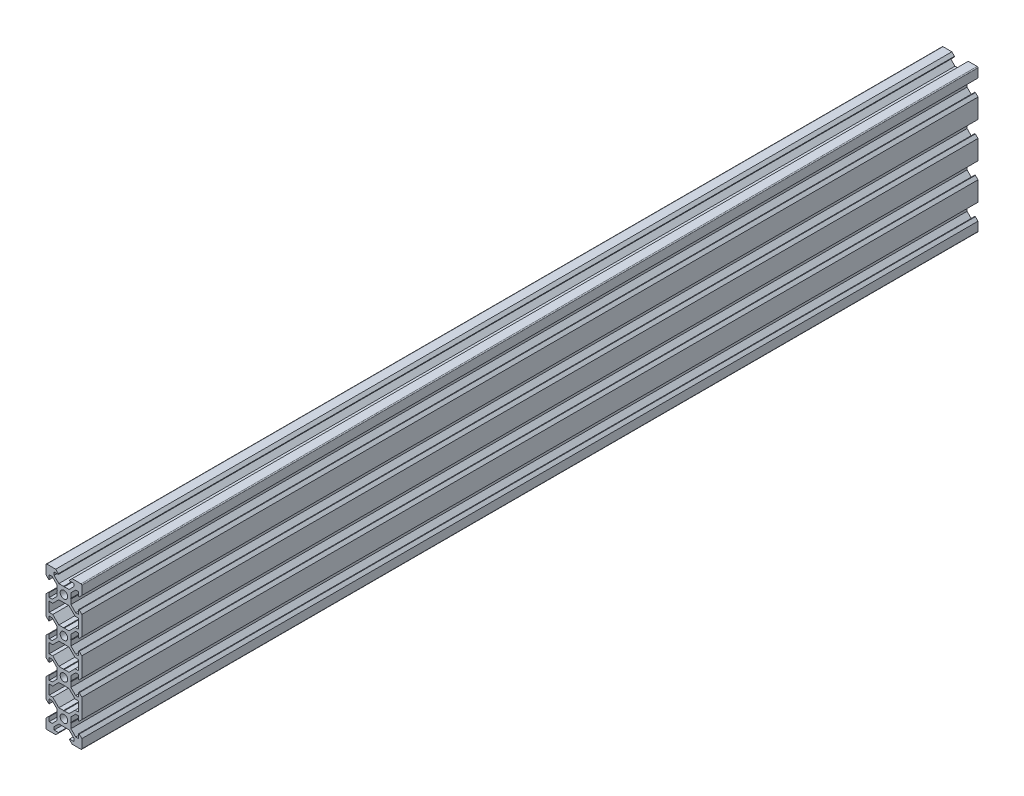
SolidWorks part; units mm, degrees
ref_plane "Plan de face" through (0, 0, 0) normal (0, 0, 1) x (1, 0, 0)
ref_plane "Plan de dessus" through (0, 0, 0) normal (0, 1, 0) x (1, 0, 0)
ref_plane "Plan de droite" through (0, 0, 0) normal (1, 0, 0) x (0, 0, -1)
ref_axis "Axe" through (0, 0, -13.782) along (0, 0, 1)
sketch "Esquisse1" plane through (0, 0, 0) normal (0, 0, 1) x (1, 0, 0)
  line L0 (0, 27.6392) -> (0, -27.6392) construction
  line L1 (-33.6074, 0) -> (33.6074, 0) construction
  line L2 (0, 0) -> (-22.2114, 22.2114) construction
  line L3 (-9.5, 10) -> (-4.58, 10)
  line L4 (-4.58, 10) -> (-3.125, 8.545)
  line L5 (-3.125, 8.545) -> (-3.125, 8.2)
  line L6 (-3.125, 8.2) -> (-5.5, 8.2)
  line L7 (-2.8393, 3.9) -> (-5.5, 6.5607)
  line L8 (-2.8393, 3.9) -> (-0.21, 3.9)
  line L9 (-5.5, 6.5607) -> (-5.5, 8.2)
  line L10 (0, 3.69) -> (0, 2.1)
  line L11 (-3.9, 2.8393) -> (-6.5607, 5.5)
  line L12 (-8.545, 3.125) -> (-8.2, 3.125)
  line L13 (-8.2, 3.125) -> (-8.2, 5.5)
  line L14 (-6.5607, 5.5) -> (-8.2, 5.5)
  line L15 (-10, 4.58) -> (-8.545, 3.125)
  line L16 (-10, 9.5) -> (-10, 4.58)
  line L17 (-0.21, 3.9) -> (0, 3.69)
  line L18 (-3.9, 2.8393) -> (-3.9, 0.21)
  line L19 (-6.2393, -12.7) -> (-8.2, -12.7)
  line L20 (-3.9, 0.21) -> (-3.69, 0)
  line L21 (-0.21, -3.9) -> (0, -3.69)
  line L22 (0, -3.69) -> (0, -2.1)
  line L23 (-6.5607, -5.5) -> (-8.2, -5.5)
  line L24 (-2.8393, -3.9) -> (-0.21, -3.9)
  line L25 (-8.545, -3.125) -> (-8.2, -3.125)
  line L26 (-10, -4.58) -> (-8.545, -3.125)
  line L27 (-8.2, -3.125) -> (-8.2, -5.5)
  line L28 (-2.8393, -3.9) -> (-6.2393, -7.3)
  line L29 (-3.9, -2.8393) -> (-6.5607, -5.5)
  line L30 (-3.9, -2.8393) -> (-3.9, -0.21)
  line L31 (-3.9, -0.21) -> (-3.69, 0)
  line L32 (-6.2393, -7.3) -> (-8.2, -7.3)
  line L33 (-8.2, -7.3) -> (-8.2, -12.7)
  line L34 (-8.2, -10) -> (-10, -10) construction
  line L35 (-10, -15.42) -> (-10, -4.58)
  line L36 (-3.9, -19.79) -> (-3.69, -20)
  line L37 (-3.9, -17.1607) -> (-3.9, -19.79)
  line L38 (-3.9, -17.1607) -> (-6.5607, -14.5)
  line L39 (-2.8393, -16.1) -> (-6.2393, -12.7)
  line L40 (-8.2, -16.875) -> (-8.2, -14.5)
  line L41 (-10, -15.42) -> (-8.545, -16.875)
  line L42 (-8.545, -16.875) -> (-8.2, -16.875)
  line L43 (-2.8393, -16.1) -> (-0.21, -16.1)
  line L44 (-6.5607, -14.5) -> (-8.2, -14.5)
  line L45 (0, -16.31) -> (0, -17.9)
  line L46 (-0.21, -16.1) -> (0, -16.31)
  line L47 (-8.2, -30) -> (-10, -30) construction
  line L48 (-3.69, -20) -> (0, -20) construction
  line L49 (-0.21, -23.9) -> (0, -23.69)
  line L50 (0, -23.69) -> (0, -22.1)
  line L51 (-6.5607, -25.5) -> (-8.2, -25.5)
  line L52 (-2.8393, -23.9) -> (-0.21, -23.9)
  line L53 (-8.545, -23.125) -> (-8.2, -23.125)
  line L54 (-10, -24.58) -> (-8.545, -23.125)
  line L55 (-8.2, -23.125) -> (-8.2, -25.5)
  line L56 (-2.8393, -23.9) -> (-6.2393, -27.3)
  line L57 (-3.9, -22.8393) -> (-6.5607, -25.5)
  line L58 (-3.9, -22.8393) -> (-3.9, -20.21)
  line L59 (-3.9, -20.21) -> (-3.69, -20)
  line L60 (-10, -24.58) -> (-10, -35.42)
  line L61 (-8.2, -32.7) -> (-8.2, -27.3)
  line L62 (-3.69, -40) -> (0, -40) construction
  line L63 (-8.2, -50) -> (-10, -50) construction
  line L64 (0, -60) -> (-22.2114, -82.2114) construction
  line L65 (-33.6074, -60) -> (33.6074, -60) construction
  line L66 (0, -87.6392) -> (0, -32.3608) construction
  line L67 (-6.2393, -32.7) -> (-8.2, -32.7)
  line L68 (-3.9, -39.79) -> (-3.69, -40)
  line L69 (-3.9, -37.1607) -> (-3.9, -39.79)
  line L70 (-3.9, -37.1607) -> (-6.5607, -34.5)
  line L71 (-2.8393, -36.1) -> (-6.2393, -32.7)
  line L72 (-8.2, -36.875) -> (-8.2, -34.5)
  line L73 (-10, -35.42) -> (-8.545, -36.875)
  line L74 (-8.545, -36.875) -> (-8.2, -36.875)
  line L75 (-6.2393, -27.3) -> (-8.2, -27.3)
  line L76 (-2.8393, -36.1) -> (-0.21, -36.1)
  line L77 (-6.5607, -34.5) -> (-8.2, -34.5)
  line L78 (0, -36.31) -> (0, -37.9)
  line L79 (-0.21, -36.1) -> (0, -36.31)
  line L80 (-0.21, -43.9) -> (0, -43.69)
  line L81 (0, -43.69) -> (0, -42.1)
  line L82 (-6.5607, -45.5) -> (-8.2, -45.5)
  line L83 (-2.8393, -43.9) -> (-0.21, -43.9)
  line L84 (-8.545, -43.125) -> (-8.2, -43.125)
  line L85 (-10, -44.58) -> (-8.545, -43.125)
  line L86 (-8.2, -43.125) -> (-8.2, -45.5)
  line L87 (-2.8393, -43.9) -> (-6.2393, -47.3)
  line L88 (-3.9, -42.8393) -> (-6.5607, -45.5)
  line L89 (-3.9, -42.8393) -> (-3.9, -40.21)
  line L90 (-3.9, -40.21) -> (-3.69, -40)
  line L91 (-10, -44.58) -> (-10, -55.42)
  line L92 (-8.2, -52.7) -> (-8.2, -47.3)
  line L93 (-6.2393, -52.7) -> (-8.2, -52.7)
  line L94 (-3.9, -59.79) -> (-3.69, -60)
  line L95 (-3.9, -57.1607) -> (-3.9, -59.79)
  line L96 (-3.9, -57.1607) -> (-6.5607, -54.5)
  line L97 (-2.8393, -56.1) -> (-6.2393, -52.7)
  line L98 (-8.2, -56.875) -> (-8.2, -54.5)
  line L99 (-10, -55.42) -> (-8.545, -56.875)
  line L100 (-8.545, -56.875) -> (-8.2, -56.875)
  line L101 (-2.8393, -56.1) -> (-0.21, -56.1)
  line L102 (-6.5607, -54.5) -> (-8.2, -54.5)
  line L103 (0, -56.31) -> (0, -57.9)
  line L104 (-0.21, -56.1) -> (0, -56.31)
  line L105 (-3.9, -60.21) -> (-3.69, -60)
  line L106 (-6.2393, -47.3) -> (-8.2, -47.3)
  line L107 (-3.9, -62.8393) -> (-3.9, -60.21)
  line L108 (-0.21, -63.9) -> (0, -63.69)
  line L109 (-10, -69.5) -> (-10, -64.58)
  line L110 (-10, -64.58) -> (-8.545, -63.125)
  line L111 (-6.5607, -65.5) -> (-8.2, -65.5)
  line L112 (-8.2, -63.125) -> (-8.2, -65.5)
  line L113 (-8.545, -63.125) -> (-8.2, -63.125)
  line L114 (-3.9, -62.8393) -> (-6.5607, -65.5)
  line L115 (0, -63.69) -> (0, -62.1)
  line L116 (-5.5, -66.5607) -> (-5.5, -68.2)
  line L117 (-2.8393, -63.9) -> (-0.21, -63.9)
  line L118 (-2.8393, -63.9) -> (-5.5, -66.5607)
  line L119 (-3.125, -68.2) -> (-5.5, -68.2)
  line L120 (-3.125, -68.545) -> (-3.125, -68.2)
  line L121 (-4.58, -70) -> (-3.125, -68.545)
  line L122 (-9.5, -70) -> (-4.58, -70)
  arc A0 (0, -2.1) -> (0, 2.1) centre (0, 0) cw
  arc A1 (-9.5, 10) -> (-10, 9.5) centre (-9.5, 9.5) ccw
  arc A2 (0, -42.1) -> (0, -37.9) centre (0, -40) cw
  arc A3 (-9.5, -70) -> (-10, -69.5) centre (-9.5, -69.5) cw
  arc A4 (0, -17.9) -> (0, -22.1) centre (0, -20) ccw
  arc A5 (0, -57.9) -> (0, -62.1) centre (0, -60) ccw
  point P4 (0, 0)
  point P7 (0, 0)
  point P30 (-10, 10)
  point P60 (0, -20)
  point P146 (-10, -70)
  dimension "D5" = 11
  dimension "D2" = 2.1
  dimension "D3" = 6.25
  dimension "D10" = 0.5
  dimension "D4" = 9.16
  dimension "D6" = 1.5
  dimension "D7" = 1.8
  dimension "D8" = 4.3
  dimension "D9" = 20
  dimension "D11" = 0.42
  dimension "D12" = 10
  dimension "D13" = 1.8
extrude "Boss.-Extru.1" add sketch "Esquisse1" along normal blind 500
sketch "Esquisse3" plane through (0, 0, 500) normal (0, 0, 1) x (1, 0, 0)
  line L0 (0, 0) -> (-9.8536, 9.8536) construction
  line L1 (-8.2, 8.2) -> (-8.2, 6.57)
  line L2 (-8.2, 6.57) -> (-7.54, 6.57)
  line L3 (-7.54, 6.57) -> (-6.57, 7.54)
  line L4 (-8.2, 3.125) -> (-8.2, 5.5) construction
  line L5 (-6.57, 8.2) -> (-6.57, 7.54)
  line L6 (-8.2, 8.2) -> (-6.57, 8.2)
  line L7 (-5.5, 6.5607) -> (-5.5, 8.2) construction
  line L8 (-10, -30) -> (6.918, -30) construction
  line L9 (-10, -24.58) -> (-10, -35.42) construction
  line L10 (-8.2, -68.2) -> (-6.57, -68.2)
  line L11 (-6.57, -68.2) -> (-6.57, -67.54)
  line L12 (-7.54, -66.57) -> (-6.57, -67.54)
  line L13 (-8.2, -66.57) -> (-7.54, -66.57)
  line L14 (-8.2, -68.2) -> (-8.2, -66.57)
  arc A0 (-9.5, 10) -> (-10, 9.5) centre (-9.5, 9.5) ccw construction
  point P13 (-7.055, 7.055)
  point P14 (-6.57, 7.87)
  point P26 (-7.055, -67.055)
  dimension "D1" = 1.07
extrude "Enlèv. mat.-Extru.1" [suppressed] cut sketch "Esquisse3" against normal through all
mirror "Symétrie1" about plane through (0, 3.69, 500) normal (-1, 0, 0) of "Enlèv. mat.-Extru.1", "Boss.-Extru.1"
